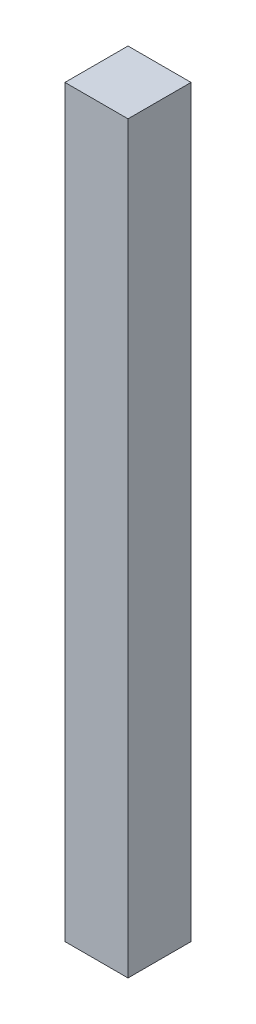
SolidWorks part; units mm, degrees
ref_plane "Front Plane" through (0, 0, 0) normal (0, 0, 1) x (1, 0, 0)
ref_plane "Top Plane" through (0, 0, 0) normal (0, 1, 0) x (1, 0, 0)
ref_plane "Right Plane" through (0, 0, 0) normal (1, 0, 0) x (0, 0, -1)
sketch "Sketch1" plane through (0, 0, 0) normal (0, 1, 0) x (1, 0, 0)
  line L1 (0, 0) -> (25.4, 0)
  line L2 (0, 0) -> (0, 25.4)
  line L3 (0, 25.4) -> (25.4, 25.4)
  line L4 (25.4, 0) -> (25.4, 25.4)
  dimension "D1" = 25.4
  dimension "D2" = 25.4
extrude "Boss-Extrude1" add sketch "Sketch1" along normal blind 299.72
